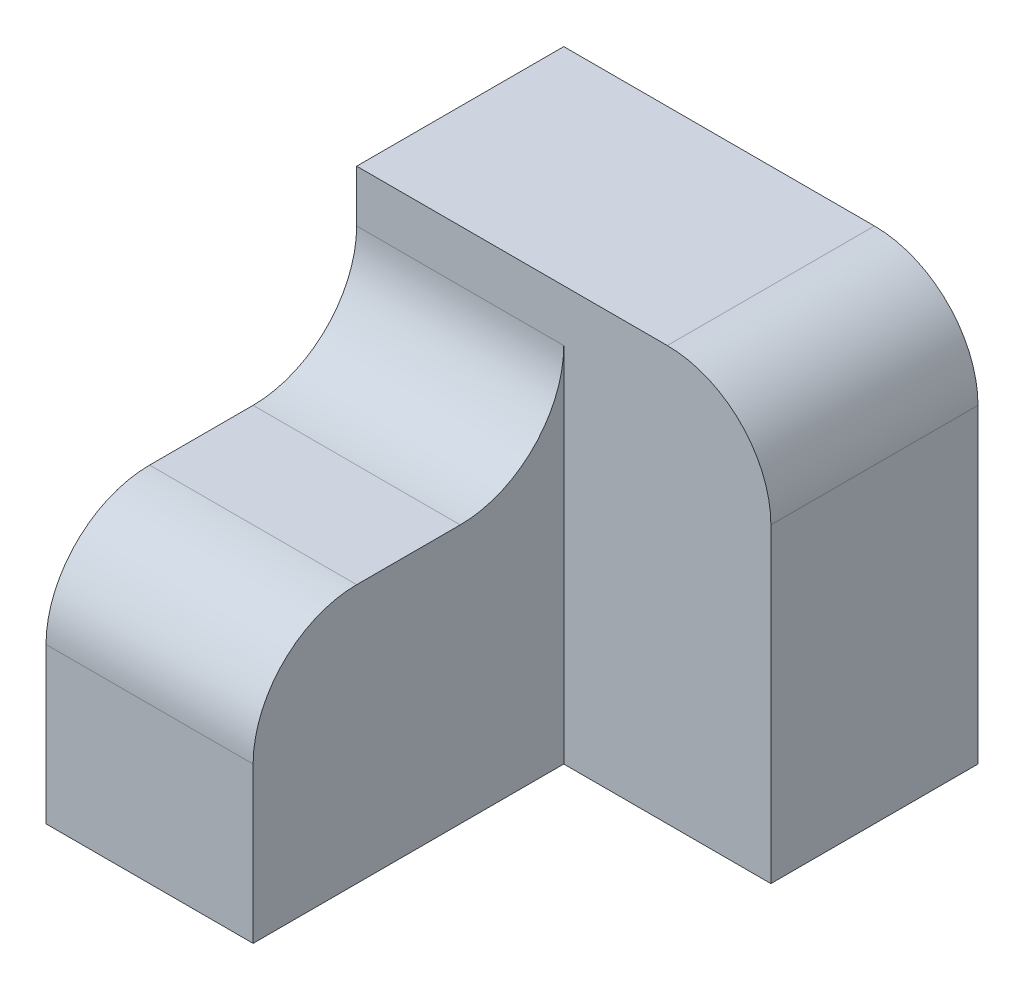
SolidWorks part; units mm, degrees
ref_plane "Front Plane" through (0, 0, 0) normal (0, 0, 1) x (1, 0, 0)
ref_plane "Top Plane" through (0, 0, 0) normal (0, 1, 0) x (1, 0, 0)
ref_plane "Right Plane" through (0, 0, 0) normal (1, 0, 0) x (0, 0, -1)
sketch "Sketch1" plane through (0, 0, 0) normal (0, 0, 1) x (1, 0, 0)
  line L1 (-30, -25) -> (-10, -25)
  line L2 (-10, -25) -> (-10, 0)
  line L3 (-10, 0) -> (-30, 0)
  line L4 (-30, 0) -> (-30, -25)
  dimension "D1" = 20
  dimension "Width" = 25
extrude "Boss-Extrude1" add sketch "Sketch1" along normal blind 30
sketch "Sketch2" plane through (0, 0, 0) normal (0, 0, 1) x (1, 0, 0)
  line L1 (-30, -25) -> (10, -25)
  line L2 (10, -25) -> (10, 15)
  line L3 (10, 15) -> (-30, 15)
  line L4 (-30, 15) -> (-30, -25)
  dimension "D1" = 40
  dimension "Width" = 40
extrude "Boss-Extrude2" add sketch "Sketch2" against normal blind 20
fillet "Fillet1" radius 10 3 edges at (-20, 0, 0) (10, 15, -10) (-20, 0, 30)
